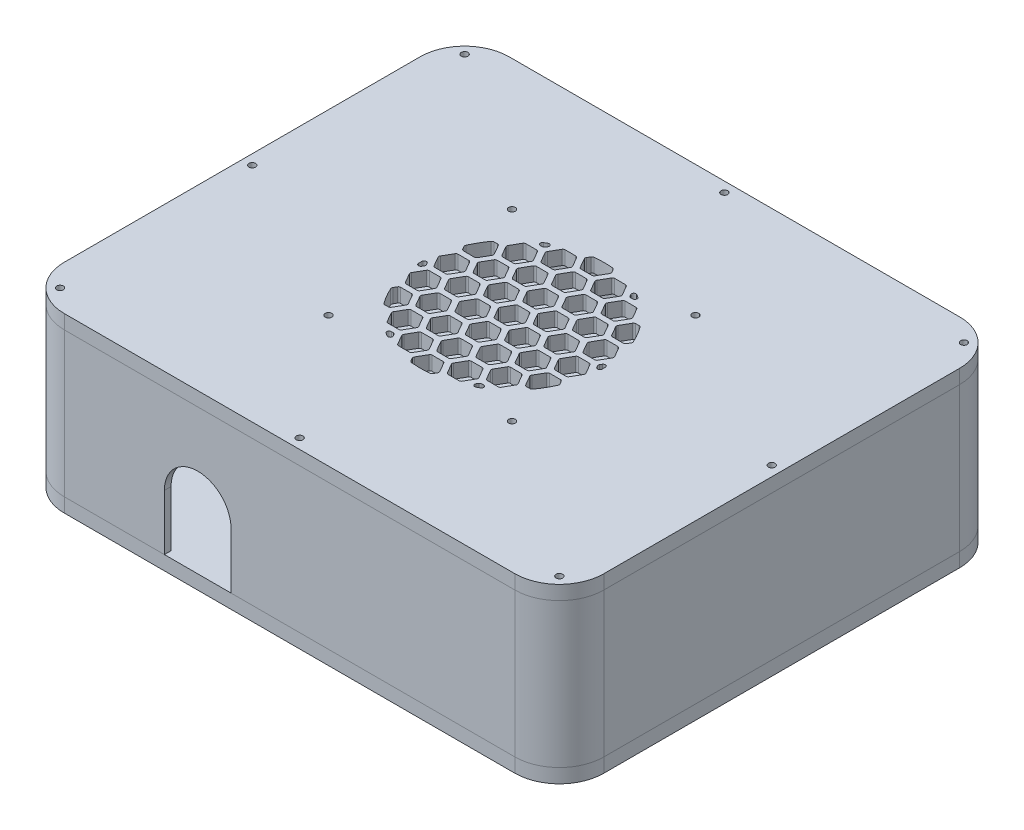
SolidWorks part; units mm, degrees
ref_plane "Front Plane" through (0, 0, 0) normal (0, 0, 1) x (1, 0, 0)
ref_plane "Top Plane" through (0, 0, 0) normal (0, 1, 0) x (1, 0, 0)
ref_plane "Right Plane" through (0, 0, 0) normal (1, 0, 0) x (0, 0, -1)
sketch "Sketch1" plane through (0, 0, 0) normal (0, 1, 0) x (1, 0, 0)
  line L0 (0, 100) -> (242.6, 100) construction
  line L1 (0, 0) -> (242.6, 0)
  line L2 (0, 0) -> (0, 200)
  line L3 (0, 200) -> (242.6, 200)
  line L4 (242.6, 0) -> (242.6, 200)
  line L6 (89, 170) -> (165.6, 170) construction
  line L7 (89, 170) -> (89, 15) construction
  line L8 (89, 15) -> (165.6, 15) construction
  line L9 (165.6, 170) -> (165.6, 15) construction
  line L10 (15, 106) -> (84, 106) construction
  line L11 (15, 106) -> (15, 15) construction
  line L12 (15, 15) -> (84, 15) construction
  line L13 (84, 106) -> (84, 15) construction
  line L14 (170.6, 184.9915) -> (230.6, 184.9915) construction
  line L15 (170.6, 184.9915) -> (170.6, 72.9915) construction
  line L16 (170.6, 72.9915) -> (230.6, 72.9915) construction
  line L17 (230.6, 184.9915) -> (230.6, 72.9915) construction
  line L22 (15, 170) -> (84, 170) construction
  line L23 (15, 170) -> (15, 121) construction
  line L24 (15, 121) -> (84, 121) construction
  line L25 (84, 170) -> (84, 121) construction
  dimension "D1" = 76.6
  dimension "D2" = 155
  dimension "D3" = 69
  dimension "D4" = 91
  dimension "D5" = 60
  dimension "D6" = 112
  dimension "D7" = 15
  dimension "D8" = 5
  dimension "D9" = 5
  dimension "D10" = 12
  dimension "D11" = 30
  dimension "D12" = 15
  dimension "D13" = 15
extrude "Boss-Extrude1" add sketch "Sketch1" along normal blind 6.35
fillet "Fillet1" radius 20 4 edges at (0, 3.175, -200) (242.6, 3.175, -200) (242.6, 3.175, 0) (0, 3.175, 0)
sketch "Sketch2" plane through (0, 6.35, 0) normal (0, 1, 0) x (1, 0, 0)
  line L0 (89, 170) -> (165.6, 170) construction
  line L1 (92.6, 160) -> (162, 160) construction
  line L2 (92.6, 160) -> (92.6, 18) construction
  line L3 (92.6, 18) -> (162, 18) construction
  line L4 (162, 160) -> (162, 18) construction
  line L5 (170.6, 184.9915) -> (230.6, 184.9915) construction
  line L6 (175.6, 150) -> (225.6, 150) construction
  line L7 (175.6, 150) -> (175.6, 125) construction
  line L8 (175.6, 125) -> (225.6, 125) construction
  line L9 (225.6, 150) -> (225.6, 125) construction
  line L10 (0, 200) -> (242.6, 200) construction
  line L11 (15, 170) -> (15, 121) construction
  line L12 (80.996, 125.18) -> (18.004, 125.18) construction
  line L13 (80.996, 125.18) -> (80.996, 165.82) construction
  line L14 (80.996, 165.82) -> (18.004, 165.82) construction
  line L15 (18.004, 125.18) -> (18.004, 165.82) construction
  line L16 (80.996, 125.18) -> (18.004, 165.82) construction
  line L17 (80.996, 165.82) -> (18.004, 125.18) construction
  line L18 (15, 170) -> (84, 170) construction
  line L19 (89, 15) -> (165.6, 15) construction
  circle A0 centre (92.6, 160) radius 1.5
  circle A1 centre (92.6, 18) radius 1.5
  circle A2 centre (162, 18) radius 1.5
  circle A3 centre (162, 160) radius 1.5
  circle A4 centre (175.6, 150) radius 1.5
  circle A5 centre (175.6, 125) radius 1.5
  circle A6 centre (225.6, 150) radius 1.5
  circle A7 centre (225.6, 125) radius 1.5
  circle A8 centre (18.004, 165.82) radius 1.5
  circle A9 centre (80.996, 165.82) radius 1.5
  circle A10 centre (80.996, 125.18) radius 1.5
  circle A11 centre (18.004, 125.18) radius 1.5
  point P6 (127.3, 160)
  point P7 (127.3, 170)
  point P20 (200.6, 150)
  point P23 (200.6, 184.9915)
  point P26 (49.5, 145.5)
  point P34 (15, 145.5)
  point P37 (49.5, 170)
  dimension "D6" = 3
  dimension "D1" = 69.4
  dimension "D2" = 142
  dimension "D3" = 3
  dimension "D4" = 50
  dimension "D5" = 25
  dimension "D7" = 50
  dimension "D8" = 62.992
  dimension "D9" = 40.64
extrude "Cut-Extrude1" cut sketch "Sketch2" against normal through all
sketch "Sketch3" plane through (0, 6.35, 0) normal (0, 1, 0) x (1, 0, 0)
  line L21 (20, 20) -> (9.0398, 9.0398) construction
  line L22 (0, 180) -> (0, 20) construction
  line L23 (6.565, 11.5147) -> (5.7618, 10.7116)
  line L24 (11.5147, 6.565) -> (10.7116, 5.7618)
  line L25 (0, 100) -> (242.6, 100) construction
  line L26 (121.3, 200) -> (121.3, 0) construction
  line L27 (231.0853, 6.565) -> (231.8884, 5.7618)
  line L28 (236.035, 11.5147) -> (236.8382, 10.7116)
  line L29 (236.035, 188.4853) -> (236.8382, 189.2884)
  line L30 (231.0853, 193.435) -> (231.8884, 194.2382)
  line L31 (11.5147, 193.435) -> (10.7116, 194.2382)
  line L32 (6.565, 188.4853) -> (5.7618, 189.2884)
  line L33 (242.6, 20) -> (242.6, 180) construction
  line L34 (20, 0) -> (222.6, 0) construction
  line L35 (222.6, 200) -> (20, 200) construction
  line L36 (20, 20) -> (20, 12.5101) construction
  line L37 (3, 180) -> (3, 20)
  line L38 (20, 3) -> (222.6, 3)
  line L39 (239.6, 20) -> (239.6, 180)
  line L40 (222.6, 197) -> (20, 197)
  line L41 (222.6, 200) -> (20, 200)
  line L42 (0, 180) -> (0, 20)
  line L43 (20, 0) -> (222.6, 0)
  line L44 (242.6, 20) -> (242.6, 180)
  line L45 (222.6, 200) -> (20, 200)
  line L46 (0, 180) -> (0, 20)
  line L47 (20, 0) -> (222.6, 0)
  line L48 (242.6, 20) -> (242.6, 180)
  line L49 (4.5, 103.5) -> (3, 103.5)
  line L50 (3, 103.5) -> (3, 96.5)
  line L51 (3, 96.5) -> (4.5, 96.5)
  line L52 (239.6, 103.5) -> (239.6, 96.5)
  line L53 (238.1, 103.5) -> (239.6, 103.5)
  line L54 (239.6, 96.5) -> (238.1, 96.5)
  line L55 (117.8, 195.5) -> (117.8, 197)
  line L56 (124.8, 195.5) -> (124.8, 197)
  line L57 (117.8, 197) -> (124.8, 197)
  line L58 (117.8, 4.5) -> (117.8, 3)
  line L59 (124.8, 4.5) -> (124.8, 3)
  line L60 (117.8, 3) -> (124.8, 3)
  arc A22 (10.7116, 194.2382) -> (5.7618, 189.2884) centre (20, 180) ccw
  arc A24 (5.7618, 10.7116) -> (10.7116, 5.7618) centre (20, 20) ccw
  arc A26 (231.8884, 5.7618) -> (236.8382, 10.7116) centre (222.6, 20) ccw
  arc A28 (236.8382, 189.2884) -> (231.8884, 194.2382) centre (222.6, 180) ccw
  arc A43 (11.5147, 6.565) -> (6.565, 11.5147) centre (9.0398, 9.0398) ccw
  circle A44 centre (9.0398, 9.0398) radius 1.5
  circle A45 centre (233.5602, 9.0398) radius 1.5
  arc A46 (231.0853, 6.565) -> (236.035, 11.5147) centre (233.5602, 9.0398) cw
  circle A47 centre (233.5602, 190.9602) radius 1.5
  arc A48 (231.0853, 193.435) -> (236.035, 188.4853) centre (233.5602, 190.9602) ccw
  circle A49 centre (9.0398, 190.9602) radius 1.5
  arc A50 (11.5147, 193.435) -> (6.565, 188.4853) centre (9.0398, 190.9602) cw
  arc A51 (222.6, 0) -> (242.6, 20) centre (222.6, 20) ccw construction
  arc A52 (0, 20) -> (20, 0) centre (20, 20) ccw construction
  arc A53 (242.6, 180) -> (222.6, 200) centre (222.6, 180) ccw construction
  arc A54 (20, 200) -> (0, 180) centre (20, 180) ccw construction
  arc A55 (3, 20) -> (20, 3) centre (20, 20) ccw
  arc A56 (222.6, 3) -> (239.6, 20) centre (222.6, 20) ccw
  arc A57 (239.6, 180) -> (222.6, 197) centre (222.6, 180) ccw
  arc A58 (20, 197) -> (3, 180) centre (20, 180) ccw
  arc A59 (20, 200) -> (0, 180) centre (20, 180) ccw
  arc A60 (0, 20) -> (20, 0) centre (20, 20) ccw
  arc A61 (222.6, 0) -> (242.6, 20) centre (222.6, 20) ccw
  arc A62 (242.6, 180) -> (222.6, 200) centre (222.6, 180) ccw
  arc A63 (20, 200) -> (0, 180) centre (20, 180) ccw
  arc A64 (0, 20) -> (20, 0) centre (20, 20) ccw
  arc A65 (222.6, 0) -> (242.6, 20) centre (222.6, 20) ccw
  arc A66 (242.6, 180) -> (222.6, 200) centre (222.6, 180) ccw
  arc A67 (4.5, 96.5) -> (4.5, 103.5) centre (4.5, 100) ccw
  circle A68 centre (4.5, 100) radius 1.5
  arc A69 (238.1, 96.5) -> (238.1, 103.5) centre (238.1, 100) cw
  circle A70 centre (238.1, 100) radius 1.5
  circle A71 centre (121.3, 195.5) radius 1.5
  arc A72 (117.8, 195.5) -> (124.8, 195.5) centre (121.3, 195.5) ccw
  circle A73 centre (121.3, 4.5) radius 1.5
  arc A74 (117.8, 4.5) -> (124.8, 4.5) centre (121.3, 4.5) cw
  line M50 (222.6, 200) -> (20, 200)
  arc M51 (20, 200) -> (0, 180) centre (20, 180) ccw
  line M52 (0, 180) -> (0, 20)
  arc M53 (0, 20) -> (20, 0) centre (20, 20) ccw
  line M54 (20, 0) -> (222.6, 0)
  arc M55 (222.6, 0) -> (242.6, 20) centre (222.6, 20) ccw
  line M56 (242.6, 20) -> (242.6, 180)
  arc M57 (242.6, 180) -> (222.6, 200) centre (222.6, 180) ccw
  dimension "D3" = 0
  dimension "D4" = 7
  dimension "D5" = 3
  dimension "D1" = 3
  dimension "D7" = 3
  dimension "D6" = 3
  dimension "D2" = 45
extrude "Boss-Extrude2" add sketch "Sketch3" along normal blind 65 separate body contours M57 M50 M51 M52 M53 M54 M55 M56 | A50 L31 A22 A49 L32 | L37 A68 L50 L51 A67 L49 | A24 A44 L24 A43 L23 | A46 L27 A26 A45 L28 | A74 L58 L38 A73 L60 L59 | L39 A70 L52 L53 A69 L54 | L30 A48 L29 A28 A47 | L55 A72 L56 L40 A71 L57 region at (11.4469, 6.35, -11.4469) region at (3.086, 6.35, -98.25) region at (117.886, 6.35, -3.75) region at (6.8741, 6.35, -190.6517) region at (231.5546, 6.35, -6.2312) region at (119.55, 6.35, -196.914) region at (238.85, 6.35, -96.586) region at (233.2517, 6.35, -193.1259) region at (236.5198, 6.35, -193.9198)
fillet "Fillet5" radius 2 16 edges at (10.7116, 38.85, -194.2382) (5.7618, 38.85, -189.2884) (3, 38.85, -103.5) (3, 38.85, -96.5) (5.7618, 38.85, -10.7116) (10.7116, 38.85, -5.7618) (117.8, 38.85, -3) (124.8, 38.85, -3) (231.8884, 38.85, -5.7618) (236.8382, 38.85, -10.7116) (239.6, 38.85, -96.5) (239.6, 38.85, -103.5) (231.8884, 38.85, -194.2382) (124.8, 38.85, -197) (117.8, 38.85, -197) (236.8382, 38.85, -189.2884)
sketch "Sketch4" plane through (0, 71.35, 0) normal (0, 1, 0) x (1, 0, 0)
  line L4 (0, 180) -> (0, 20)
  line L5 (222.6, 200) -> (20, 200)
  line L6 (242.6, 20) -> (242.6, 180)
  line L7 (20, 0) -> (222.6, 0)
  line L8 (0, 180) -> (0, 20)
  line L9 (222.6, 200) -> (20, 200)
  line L10 (242.6, 20) -> (242.6, 180)
  line L11 (20, 0) -> (222.6, 0)
  arc A4 (20, 200) -> (0, 180) centre (20, 180) ccw
  arc A5 (242.6, 180) -> (222.6, 200) centre (222.6, 180) ccw
  arc A6 (222.6, 0) -> (242.6, 20) centre (222.6, 20) ccw
  arc A7 (0, 20) -> (20, 0) centre (20, 20) ccw
  arc A8 (20, 200) -> (0, 180) centre (20, 180) ccw
  arc A9 (242.6, 180) -> (222.6, 200) centre (222.6, 180) ccw
  arc A10 (222.6, 0) -> (242.6, 20) centre (222.6, 20) ccw
  arc A11 (0, 20) -> (20, 0) centre (20, 20) ccw
  dimension "D1" = 0
extrude "Boss-Extrude4" add sketch "Sketch4" along normal blind 6.35 separate body
sketch "Sketch5" plane through (0, 77.7, 0) normal (0, 1, 0) x (1, 0, 0)
  line L1 (80.05, 141.25) -> (162.55, 141.25) construction
  line L2 (80.05, 141.25) -> (80.05, 58.75) construction
  line L3 (80.05, 58.75) -> (162.55, 58.75) construction
  line L4 (162.55, 141.25) -> (162.55, 58.75) construction
  line L5 (80.05, 141.25) -> (162.55, 58.75) construction
  line L6 (80.05, 58.75) -> (162.55, 141.25) construction
  line L8 (222.6, 200) -> (20, 200) construction
  line L9 (0, 180) -> (0, 20) construction
  circle A0 centre (80.05, 141.25) radius 1.5
  circle A1 centre (80.05, 58.75) radius 1.5
  circle A2 centre (162.55, 58.75) radius 1.5
  circle A3 centre (162.55, 141.25) radius 1.5
  point P0 (121.3, 100)
  point P11 (121.3, 200)
  point P12 (0, 100)
  dimension "D2" = 3
  dimension "D1" = 82.5
extrude "Cut-Extrude2" cut sketch "Sketch5" against normal through all
sketch "Sketch6" plane through (0, 77.7, 0) normal (0, 1, 0) x (1, 0, 0)
  circle A20 centre (121.3, 4.5) radius 1.5 construction
  circle A21 centre (233.5602, 9.0398) radius 1.5 construction
  circle A22 centre (238.1, 100) radius 1.5 construction
  circle A23 centre (233.5602, 190.9602) radius 1.5 construction
  circle A24 centre (121.3, 195.5) radius 1.5 construction
  circle A25 centre (9.0398, 190.9602) radius 1.5 construction
  circle A26 centre (4.5, 100) radius 1.5 construction
  circle A27 centre (9.0398, 9.0398) radius 1.5 construction
  circle A28 centre (121.3, 4.5) radius 1.5
  circle A29 centre (233.5602, 9.0398) radius 1.5
  circle A30 centre (238.1, 100) radius 1.5
  circle A31 centre (233.5602, 190.9602) radius 1.5
  circle A32 centre (121.3, 195.5) radius 1.5
  circle A33 centre (9.0398, 190.9602) radius 1.5
  circle A34 centre (4.5, 100) radius 1.5
  circle A35 centre (9.0398, 9.0398) radius 1.5
extrude "Cut-Extrude3" cut sketch "Sketch6" against normal through all
sketch "Sketch7" plane through (0, 77.7, 0) normal (0, 1, 0) x (1, 0, 0)
  line L0 (80.05, 141.25) -> (162.55, 141.25) construction
  line L1 (80.05, 141.25) -> (80.05, 58.75) construction
  line L2 (80.05, 58.75) -> (162.55, 58.75) construction
  line L3 (162.55, 141.25) -> (162.55, 58.75) construction
  line L4 (80.05, 141.25) -> (162.55, 141.25) construction
  line L5 (80.05, 141.25) -> (80.05, 58.75) construction
  line L6 (80.05, 58.75) -> (162.55, 58.75) construction
  line L7 (162.55, 141.25) -> (162.55, 58.75) construction
  line L8 (157.7952, 124.5346) -> (151.7952, 124.5346)
  line L9 (124.3, 105.1962) -> (118.3, 105.1962)
  line L10 (118.3, 105.1962) -> (115.3, 100)
  line L11 (115.3, 100) -> (118.3, 94.8038)
  line L12 (118.3, 94.8038) -> (124.3, 94.8038)
  line L13 (124.3, 94.8038) -> (127.3, 100)
  line L14 (127.3, 100) -> (124.3, 105.1962)
  line L15 (138.4651, 106.4462) -> (135.4651, 111.6423)
  line L16 (135.4651, 111.6423) -> (129.4651, 111.6423)
  line L17 (129.4651, 111.6423) -> (126.4651, 106.4462)
  line L18 (126.4651, 106.4462) -> (129.4651, 101.25)
  line L19 (129.4651, 101.25) -> (135.4651, 101.25)
  line L20 (135.4651, 101.25) -> (138.4651, 106.4462)
  line L21 (127.3, 112.8923) -> (124.3, 118.0885)
  line L22 (124.3, 118.0885) -> (118.3, 118.0885)
  line L23 (118.3, 118.0885) -> (115.3, 112.8923)
  line L24 (115.3, 112.8923) -> (118.3, 107.6962)
  line L25 (118.3, 107.6962) -> (124.3, 107.6962)
  line L26 (124.3, 107.6962) -> (127.3, 112.8923)
  line L27 (135.4651, 124.5346) -> (129.4651, 124.5346)
  line L28 (129.4651, 124.5346) -> (126.4651, 119.3385)
  line L29 (126.4651, 119.3385) -> (129.4651, 114.1423)
  line L30 (129.4651, 114.1423) -> (135.4651, 114.1423)
  line L31 (135.4651, 114.1423) -> (138.4651, 119.3385)
  line L32 (138.4651, 119.3385) -> (135.4651, 124.5346)
  line L33 (151.7952, 124.5346) -> (148.7952, 119.3385)
  line L34 (148.7952, 119.3385) -> (151.7952, 114.1423)
  line L35 (151.7952, 114.1423) -> (157.7952, 114.1423)
  line L36 (157.7952, 114.1423) -> (160.7952, 119.3385)
  line L37 (160.7952, 119.3385) -> (157.7952, 124.5346)
  line L38 (149.6301, 112.8923) -> (146.6301, 118.0885)
  line L39 (146.6301, 118.0885) -> (140.6301, 118.0885)
  line L40 (140.6301, 118.0885) -> (137.6301, 112.8923)
  line L41 (137.6301, 112.8923) -> (140.6301, 107.6962)
  line L42 (140.6301, 107.6962) -> (146.6301, 107.6962)
  line L43 (146.6301, 107.6962) -> (149.6301, 112.8923)
  line L44 (146.6301, 105.1962) -> (140.6301, 105.1962)
  line L45 (140.6301, 105.1962) -> (137.6301, 100)
  line L46 (137.6301, 100) -> (140.6301, 94.8038)
  line L47 (140.6301, 94.8038) -> (146.6301, 94.8038)
  line L48 (146.6301, 94.8038) -> (149.6301, 100)
  line L49 (149.6301, 100) -> (146.6301, 105.1962)
  line L50 (160.7952, 106.4462) -> (157.7952, 111.6423)
  line L51 (157.7952, 111.6423) -> (151.7952, 111.6423)
  line L52 (151.7952, 111.6423) -> (148.7952, 106.4462)
  line L53 (148.7952, 106.4462) -> (151.7952, 101.25)
  line L54 (151.7952, 101.25) -> (157.7952, 101.25)
  line L55 (157.7952, 101.25) -> (160.7952, 106.4462)
  line L56 (180.1253, 124.5346) -> (174.1253, 124.5346)
  line L57 (174.1253, 124.5346) -> (171.1253, 119.3385)
  line L58 (171.1253, 119.3385) -> (174.1253, 114.1423)
  line L59 (174.1253, 114.1423) -> (180.1253, 114.1423)
  line L60 (180.1253, 114.1423) -> (183.1253, 119.3385)
  line L61 (183.1253, 119.3385) -> (180.1253, 124.5346)
  line L62 (171.9603, 112.8923) -> (168.9603, 118.0885)
  line L63 (168.9603, 118.0885) -> (162.9603, 118.0885)
  line L64 (162.9603, 118.0885) -> (159.9603, 112.8923)
  line L65 (159.9603, 112.8923) -> (162.9603, 107.6962)
  line L66 (162.9603, 107.6962) -> (168.9603, 107.6962)
  line L67 (168.9603, 107.6962) -> (171.9603, 112.8923)
  line L68 (168.9603, 105.1962) -> (162.9603, 105.1962)
  line L69 (162.9603, 105.1962) -> (159.9603, 100)
  line L70 (159.9603, 100) -> (162.9603, 94.8038)
  line L71 (162.9603, 94.8038) -> (168.9603, 94.8038)
  line L72 (168.9603, 94.8038) -> (171.9603, 100)
  line L73 (171.9603, 100) -> (168.9603, 105.1962)
  line L74 (183.1253, 106.4462) -> (180.1253, 111.6423)
  line L75 (180.1253, 111.6423) -> (174.1253, 111.6423)
  line L76 (174.1253, 111.6423) -> (171.1253, 106.4462)
  line L77 (171.1253, 106.4462) -> (174.1253, 101.25)
  line L78 (174.1253, 101.25) -> (180.1253, 101.25)
  line L79 (180.1253, 101.25) -> (183.1253, 106.4462)
  line L80 (157.7952, 150.3192) -> (151.7952, 150.3192)
  line L81 (151.7952, 150.3192) -> (148.7952, 145.1231)
  line L82 (148.7952, 145.1231) -> (151.7952, 139.9269)
  line L83 (151.7952, 139.9269) -> (157.7952, 139.9269)
  line L84 (157.7952, 139.9269) -> (160.7952, 145.1231)
  line L85 (160.7952, 145.1231) -> (157.7952, 150.3192)
  line L86 (149.6301, 138.6769) -> (146.6301, 143.8731)
  line L87 (146.6301, 143.8731) -> (140.6301, 143.8731)
  line L88 (140.6301, 143.8731) -> (137.6301, 138.6769)
  line L89 (137.6301, 138.6769) -> (140.6301, 133.4808)
  line L90 (140.6301, 133.4808) -> (146.6301, 133.4808)
  line L91 (146.6301, 133.4808) -> (149.6301, 138.6769)
  line L92 (146.6301, 130.9808) -> (140.6301, 130.9808)
  line L93 (140.6301, 130.9808) -> (137.6301, 125.7846)
  line L94 (137.6301, 125.7846) -> (140.6301, 120.5885)
  line L95 (140.6301, 120.5885) -> (146.6301, 120.5885)
  line L96 (146.6301, 120.5885) -> (149.6301, 125.7846)
  line L97 (149.6301, 125.7846) -> (146.6301, 130.9808)
  line L98 (160.7952, 132.2308) -> (157.7952, 137.4269)
  line L99 (157.7952, 137.4269) -> (151.7952, 137.4269)
  line L100 (151.7952, 137.4269) -> (148.7952, 132.2308)
  line L101 (148.7952, 132.2308) -> (151.7952, 127.0346)
  line L102 (151.7952, 127.0346) -> (157.7952, 127.0346)
  line L103 (157.7952, 127.0346) -> (160.7952, 132.2308)
  line L104 (180.1253, 150.3192) -> (174.1253, 150.3192)
  line L105 (174.1253, 150.3192) -> (171.1253, 145.1231)
  line L106 (171.1253, 145.1231) -> (174.1253, 139.9269)
  line L107 (174.1253, 139.9269) -> (180.1253, 139.9269)
  line L108 (180.1253, 139.9269) -> (183.1253, 145.1231)
  line L109 (183.1253, 145.1231) -> (180.1253, 150.3192)
  line L110 (171.9603, 138.6769) -> (168.9603, 143.8731)
  line L111 (168.9603, 143.8731) -> (162.9603, 143.8731)
  line L112 (162.9603, 143.8731) -> (159.9603, 138.6769)
  line L113 (159.9603, 138.6769) -> (162.9603, 133.4808)
  line L114 (162.9603, 133.4808) -> (168.9603, 133.4808)
  line L115 (168.9603, 133.4808) -> (171.9603, 138.6769)
  line L116 (168.9603, 130.9808) -> (162.9603, 130.9808)
  line L117 (162.9603, 130.9808) -> (159.9603, 125.7846)
  line L118 (159.9603, 125.7846) -> (162.9603, 120.5885)
  line L119 (162.9603, 120.5885) -> (168.9603, 120.5885)
  line L120 (168.9603, 120.5885) -> (171.9603, 125.7846)
  line L121 (171.9603, 125.7846) -> (168.9603, 130.9808)
  line L122 (183.1253, 132.2308) -> (180.1253, 137.4269)
  line L123 (180.1253, 137.4269) -> (174.1253, 137.4269)
  line L124 (174.1253, 137.4269) -> (171.1253, 132.2308)
  line L125 (171.1253, 132.2308) -> (174.1253, 127.0346)
  line L126 (174.1253, 127.0346) -> (180.1253, 127.0346)
  line L127 (180.1253, 127.0346) -> (183.1253, 132.2308)
  line L128 (135.4651, 150.3192) -> (129.4651, 150.3192)
  line L129 (129.4651, 150.3192) -> (126.4651, 145.1231)
  line L130 (126.4651, 145.1231) -> (129.4651, 139.9269)
  line L131 (129.4651, 139.9269) -> (135.4651, 139.9269)
  line L132 (135.4651, 139.9269) -> (138.4651, 145.1231)
  line L133 (138.4651, 145.1231) -> (135.4651, 150.3192)
  line L134 (127.3, 138.6769) -> (124.3, 143.8731)
  line L135 (124.3, 143.8731) -> (118.3, 143.8731)
  line L136 (118.3, 143.8731) -> (115.3, 138.6769)
  line L137 (115.3, 138.6769) -> (118.3, 133.4808)
  line L138 (118.3, 133.4808) -> (124.3, 133.4808)
  line L139 (124.3, 133.4808) -> (127.3, 138.6769)
  line L140 (124.3, 130.9808) -> (118.3, 130.9808)
  line L141 (118.3, 130.9808) -> (115.3, 125.7846)
  line L142 (115.3, 125.7846) -> (118.3, 120.5885)
  line L143 (118.3, 120.5885) -> (124.3, 120.5885)
  line L144 (124.3, 120.5885) -> (127.3, 125.7846)
  line L145 (127.3, 125.7846) -> (124.3, 130.9808)
  line L146 (138.4651, 132.2308) -> (135.4651, 137.4269)
  line L147 (135.4651, 137.4269) -> (129.4651, 137.4269)
  line L148 (129.4651, 137.4269) -> (126.4651, 132.2308)
  line L149 (126.4651, 132.2308) -> (129.4651, 127.0346)
  line L150 (129.4651, 127.0346) -> (135.4651, 127.0346)
  line L151 (135.4651, 127.0346) -> (138.4651, 132.2308)
  line L152 (124.3, 92.3038) -> (118.3, 92.3038)
  line L153 (118.3, 92.3038) -> (115.3, 87.1077)
  line L154 (115.3, 87.1077) -> (118.3, 81.9115)
  line L155 (118.3, 81.9115) -> (124.3, 81.9115)
  line L156 (124.3, 81.9115) -> (127.3, 87.1077)
  line L157 (127.3, 87.1077) -> (124.3, 92.3038)
  line L158 (138.4651, 93.5538) -> (135.4651, 98.75)
  line L159 (135.4651, 98.75) -> (129.4651, 98.75)
  line L160 (129.4651, 98.75) -> (126.4651, 93.5538)
  line L161 (126.4651, 93.5538) -> (129.4651, 88.3577)
  line L162 (129.4651, 88.3577) -> (135.4651, 88.3577)
  line L163 (135.4651, 88.3577) -> (138.4651, 93.5538)
  line L164 (160.7952, 93.5538) -> (157.7952, 98.75)
  line L165 (157.7952, 98.75) -> (151.7952, 98.75)
  line L166 (151.7952, 98.75) -> (148.7952, 93.5538)
  line L167 (148.7952, 93.5538) -> (151.7952, 88.3577)
  line L168 (151.7952, 88.3577) -> (157.7952, 88.3577)
  line L169 (157.7952, 88.3577) -> (160.7952, 93.5538)
  line L170 (168.9603, 92.3038) -> (162.9603, 92.3038)
  line L171 (162.9603, 92.3038) -> (159.9603, 87.1077)
  line L172 (159.9603, 87.1077) -> (162.9603, 81.9115)
  line L173 (162.9603, 81.9115) -> (168.9603, 81.9115)
  line L174 (168.9603, 81.9115) -> (171.9603, 87.1077)
  line L175 (171.9603, 87.1077) -> (168.9603, 92.3038)
  line L176 (146.6301, 92.3038) -> (140.6301, 92.3038)
  line L177 (140.6301, 92.3038) -> (137.6301, 87.1077)
  line L178 (137.6301, 87.1077) -> (140.6301, 81.9115)
  line L179 (140.6301, 81.9115) -> (146.6301, 81.9115)
  line L180 (146.6301, 81.9115) -> (149.6301, 87.1077)
  line L181 (149.6301, 87.1077) -> (146.6301, 92.3038)
  line L182 (124.3, 79.4115) -> (118.3, 79.4115)
  line L183 (118.3, 79.4115) -> (115.3, 74.2154)
  line L184 (115.3, 74.2154) -> (118.3, 69.0192)
  line L185 (118.3, 69.0192) -> (124.3, 69.0192)
  line L186 (124.3, 69.0192) -> (127.3, 74.2154)
  line L187 (127.3, 74.2154) -> (124.3, 79.4115)
  line L188 (138.4651, 80.6615) -> (135.4651, 85.8577)
  line L189 (135.4651, 85.8577) -> (129.4651, 85.8577)
  line L190 (129.4651, 85.8577) -> (126.4651, 80.6615)
  line L191 (126.4651, 80.6615) -> (129.4651, 75.4654)
  line L192 (129.4651, 75.4654) -> (135.4651, 75.4654)
  line L193 (135.4651, 75.4654) -> (138.4651, 80.6615)
  line L194 (160.7952, 80.6615) -> (157.7952, 85.8577)
  line L195 (157.7952, 85.8577) -> (151.7952, 85.8577)
  line L196 (151.7952, 85.8577) -> (148.7952, 80.6615)
  line L197 (148.7952, 80.6615) -> (151.7952, 75.4654)
  line L198 (151.7952, 75.4654) -> (157.7952, 75.4654)
  line L199 (157.7952, 75.4654) -> (160.7952, 80.6615)
  line L200 (168.9603, 79.4115) -> (162.9603, 79.4115)
  line L201 (162.9603, 79.4115) -> (159.9603, 74.2154)
  line L202 (159.9603, 74.2154) -> (162.9603, 69.0192)
  line L203 (162.9603, 69.0192) -> (168.9603, 69.0192)
  line L204 (168.9603, 69.0192) -> (171.9603, 74.2154)
  line L205 (171.9603, 74.2154) -> (168.9603, 79.4115)
  line L206 (146.6301, 79.4115) -> (140.6301, 79.4115)
  line L207 (140.6301, 79.4115) -> (137.6301, 74.2154)
  line L208 (137.6301, 74.2154) -> (140.6301, 69.0192)
  line L209 (140.6301, 69.0192) -> (146.6301, 69.0192)
  line L210 (146.6301, 69.0192) -> (149.6301, 74.2154)
  line L211 (149.6301, 74.2154) -> (146.6301, 79.4115)
  line L212 (124.3, 66.5192) -> (118.3, 66.5192)
  line L213 (118.3, 66.5192) -> (115.3, 61.3231)
  line L214 (115.3, 61.3231) -> (118.3, 56.1269)
  line L215 (118.3, 56.1269) -> (124.3, 56.1269)
  line L216 (124.3, 56.1269) -> (127.3, 61.3231)
  line L217 (127.3, 61.3231) -> (124.3, 66.5192)
  line L218 (138.4651, 67.7692) -> (135.4651, 72.9654)
  line L219 (135.4651, 72.9654) -> (129.4651, 72.9654)
  line L220 (129.4651, 72.9654) -> (126.4651, 67.7692)
  line L221 (126.4651, 67.7692) -> (129.4651, 62.5731)
  line L222 (129.4651, 62.5731) -> (135.4651, 62.5731)
  line L223 (135.4651, 62.5731) -> (138.4651, 67.7692)
  line L224 (160.7952, 67.7692) -> (157.7952, 72.9654)
  line L225 (157.7952, 72.9654) -> (151.7952, 72.9654)
  line L226 (151.7952, 72.9654) -> (148.7952, 67.7692)
  line L227 (148.7952, 67.7692) -> (151.7952, 62.5731)
  line L228 (151.7952, 62.5731) -> (157.7952, 62.5731)
  line L229 (157.7952, 62.5731) -> (160.7952, 67.7692)
  line L230 (168.9603, 66.5192) -> (162.9603, 66.5192)
  line L231 (162.9603, 66.5192) -> (159.9603, 61.3231)
  line L232 (159.9603, 61.3231) -> (162.9603, 56.1269)
  line L233 (162.9603, 56.1269) -> (168.9603, 56.1269)
  line L234 (168.9603, 56.1269) -> (171.9603, 61.3231)
  line L235 (171.9603, 61.3231) -> (168.9603, 66.5192)
  line L236 (146.6301, 66.5192) -> (140.6301, 66.5192)
  line L237 (140.6301, 66.5192) -> (137.6301, 61.3231)
  line L238 (137.6301, 61.3231) -> (140.6301, 56.1269)
  line L239 (140.6301, 56.1269) -> (146.6301, 56.1269)
  line L240 (146.6301, 56.1269) -> (149.6301, 61.3231)
  line L241 (149.6301, 61.3231) -> (146.6301, 66.5192)
  line L242 (124.3, 53.6269) -> (118.3, 53.6269)
  line L243 (118.3, 53.6269) -> (115.3, 48.4308)
  line L244 (115.3, 48.4308) -> (118.3, 43.2346)
  line L245 (118.3, 43.2346) -> (124.3, 43.2346)
  line L246 (124.3, 43.2346) -> (127.3, 48.4308)
  line L247 (127.3, 48.4308) -> (124.3, 53.6269)
  line L248 (138.4651, 54.8769) -> (135.4651, 60.0731)
  line L249 (135.4651, 60.0731) -> (129.4651, 60.0731)
  line L250 (129.4651, 60.0731) -> (126.4651, 54.8769)
  line L251 (126.4651, 54.8769) -> (129.4651, 49.6808)
  line L252 (129.4651, 49.6808) -> (135.4651, 49.6808)
  line L253 (135.4651, 49.6808) -> (138.4651, 54.8769)
  line L254 (160.7952, 54.8769) -> (157.7952, 60.0731)
  line L255 (157.7952, 60.0731) -> (151.7952, 60.0731)
  line L256 (151.7952, 60.0731) -> (148.7952, 54.8769)
  line L257 (148.7952, 54.8769) -> (151.7952, 49.6808)
  line L258 (151.7952, 49.6808) -> (157.7952, 49.6808)
  line L259 (157.7952, 49.6808) -> (160.7952, 54.8769)
  line L260 (168.9603, 53.6269) -> (162.9603, 53.6269)
  line L261 (162.9603, 53.6269) -> (159.9603, 48.4308)
  line L262 (159.9603, 48.4308) -> (162.9603, 43.2346)
  line L263 (162.9603, 43.2346) -> (168.9603, 43.2346)
  line L264 (168.9603, 43.2346) -> (171.9603, 48.4308)
  line L265 (171.9603, 48.4308) -> (168.9603, 53.6269)
  line L266 (146.6301, 53.6269) -> (140.6301, 53.6269)
  line L267 (140.6301, 53.6269) -> (137.6301, 48.4308)
  line L268 (137.6301, 48.4308) -> (140.6301, 43.2346)
  line L269 (140.6301, 43.2346) -> (146.6301, 43.2346)
  line L270 (146.6301, 43.2346) -> (149.6301, 48.4308)
  line L271 (149.6301, 48.4308) -> (146.6301, 53.6269)
  line L272 (104.9699, 138.6769) -> (101.9699, 143.8731)
  line L273 (101.9699, 143.8731) -> (95.9699, 143.8731)
  line L274 (95.9699, 143.8731) -> (92.9699, 138.6769)
  line L275 (92.9699, 138.6769) -> (95.9699, 133.4808)
  line L276 (95.9699, 133.4808) -> (101.9699, 133.4808)
  line L277 (101.9699, 133.4808) -> (104.9699, 138.6769)
  line L278 (101.9699, 130.9808) -> (95.9699, 130.9808)
  line L279 (95.9699, 130.9808) -> (92.9699, 125.7846)
  line L280 (92.9699, 125.7846) -> (95.9699, 120.5885)
  line L281 (95.9699, 120.5885) -> (101.9699, 120.5885)
  line L282 (101.9699, 120.5885) -> (104.9699, 125.7846)
  line L283 (104.9699, 125.7846) -> (101.9699, 130.9808)
  line L284 (101.9699, 92.3038) -> (95.9699, 92.3038)
  line L285 (95.9699, 92.3038) -> (92.9699, 87.1077)
  line L286 (92.9699, 87.1077) -> (95.9699, 81.9115)
  line L287 (95.9699, 81.9115) -> (101.9699, 81.9115)
  line L288 (101.9699, 81.9115) -> (104.9699, 87.1077)
  line L289 (104.9699, 87.1077) -> (101.9699, 92.3038)
  line L290 (101.9699, 79.4115) -> (95.9699, 79.4115)
  line L291 (95.9699, 79.4115) -> (92.9699, 74.2154)
  line L292 (92.9699, 74.2154) -> (95.9699, 69.0192)
  line L293 (95.9699, 69.0192) -> (101.9699, 69.0192)
  line L294 (101.9699, 69.0192) -> (104.9699, 74.2154)
  line L295 (104.9699, 74.2154) -> (101.9699, 79.4115)
  line L296 (101.9699, 66.5192) -> (95.9699, 66.5192)
  line L297 (95.9699, 66.5192) -> (92.9699, 61.3231)
  line L298 (92.9699, 61.3231) -> (95.9699, 56.1269)
  line L299 (95.9699, 56.1269) -> (101.9699, 56.1269)
  line L300 (101.9699, 56.1269) -> (104.9699, 61.3231)
  line L301 (104.9699, 61.3231) -> (101.9699, 66.5192)
  line L302 (116.1349, 67.7692) -> (113.1349, 72.9654)
  line L303 (113.1349, 72.9654) -> (107.1349, 72.9654)
  line L304 (107.1349, 72.9654) -> (104.1349, 67.7692)
  line L305 (104.1349, 67.7692) -> (107.1349, 62.5731)
  line L306 (107.1349, 62.5731) -> (113.1349, 62.5731)
  line L307 (113.1349, 62.5731) -> (116.1349, 67.7692)
  line L308 (116.1349, 80.6615) -> (113.1349, 85.8577)
  line L309 (113.1349, 85.8577) -> (107.1349, 85.8577)
  line L310 (107.1349, 85.8577) -> (104.1349, 80.6615)
  line L311 (104.1349, 80.6615) -> (107.1349, 75.4654)
  line L312 (107.1349, 75.4654) -> (113.1349, 75.4654)
  line L313 (113.1349, 75.4654) -> (116.1349, 80.6615)
  line L314 (101.9699, 105.1962) -> (95.9699, 105.1962)
  line L315 (95.9699, 105.1962) -> (92.9699, 100)
  line L316 (92.9699, 100) -> (95.9699, 94.8038)
  line L317 (95.9699, 94.8038) -> (101.9699, 94.8038)
  line L318 (101.9699, 94.8038) -> (104.9699, 100)
  line L319 (104.9699, 100) -> (101.9699, 105.1962)
  line L320 (116.1349, 93.5538) -> (113.1349, 98.75)
  line L321 (113.1349, 98.75) -> (107.1349, 98.75)
  line L322 (107.1349, 98.75) -> (104.1349, 93.5538)
  line L323 (104.1349, 93.5538) -> (107.1349, 88.3577)
  line L324 (107.1349, 88.3577) -> (113.1349, 88.3577)
  line L325 (113.1349, 88.3577) -> (116.1349, 93.5538)
  line L326 (116.1349, 106.4462) -> (113.1349, 111.6423)
  line L327 (113.1349, 111.6423) -> (107.1349, 111.6423)
  line L328 (107.1349, 111.6423) -> (104.1349, 106.4462)
  line L329 (104.1349, 106.4462) -> (107.1349, 101.25)
  line L330 (107.1349, 101.25) -> (113.1349, 101.25)
  line L331 (113.1349, 101.25) -> (116.1349, 106.4462)
  line L332 (104.9699, 112.8923) -> (101.9699, 118.0885)
  line L333 (101.9699, 118.0885) -> (95.9699, 118.0885)
  line L334 (95.9699, 118.0885) -> (92.9699, 112.8923)
  line L335 (92.9699, 112.8923) -> (95.9699, 107.6962)
  line L336 (95.9699, 107.6962) -> (101.9699, 107.6962)
  line L337 (101.9699, 107.6962) -> (104.9699, 112.8923)
  line L338 (113.1349, 124.5346) -> (107.1349, 124.5346)
  line L339 (107.1349, 124.5346) -> (104.1349, 119.3385)
  line L340 (104.1349, 119.3385) -> (107.1349, 114.1423)
  line L341 (107.1349, 114.1423) -> (113.1349, 114.1423)
  line L342 (113.1349, 114.1423) -> (116.1349, 119.3385)
  line L343 (116.1349, 119.3385) -> (113.1349, 124.5346)
  line L344 (116.1349, 132.2308) -> (113.1349, 137.4269)
  line L345 (113.1349, 137.4269) -> (107.1349, 137.4269)
  line L346 (107.1349, 137.4269) -> (104.1349, 132.2308)
  line L347 (104.1349, 132.2308) -> (107.1349, 127.0346)
  line L348 (107.1349, 127.0346) -> (113.1349, 127.0346)
  line L349 (113.1349, 127.0346) -> (116.1349, 132.2308)
  line L350 (116.1349, 54.8769) -> (113.1349, 60.0731)
  line L351 (113.1349, 60.0731) -> (107.1349, 60.0731)
  line L352 (107.1349, 60.0731) -> (104.1349, 54.8769)
  line L353 (104.1349, 54.8769) -> (107.1349, 49.6808)
  line L354 (107.1349, 49.6808) -> (113.1349, 49.6808)
  line L355 (113.1349, 49.6808) -> (116.1349, 54.8769)
  line L356 (82.6397, 138.6769) -> (79.6397, 143.8731)
  line L357 (79.6397, 143.8731) -> (73.6397, 143.8731)
  line L358 (73.6397, 143.8731) -> (70.6397, 138.6769)
  line L359 (70.6397, 138.6769) -> (73.6397, 133.4808)
  line L360 (73.6397, 133.4808) -> (79.6397, 133.4808)
  line L361 (79.6397, 133.4808) -> (82.6397, 138.6769)
  line L362 (79.6397, 130.9808) -> (73.6397, 130.9808)
  line L363 (73.6397, 130.9808) -> (70.6397, 125.7846)
  line L364 (70.6397, 125.7846) -> (73.6397, 120.5885)
  line L365 (73.6397, 120.5885) -> (79.6397, 120.5885)
  line L366 (79.6397, 120.5885) -> (82.6397, 125.7846)
  line L367 (82.6397, 125.7846) -> (79.6397, 130.9808)
  line L368 (79.6397, 92.3038) -> (73.6397, 92.3038)
  line L369 (73.6397, 92.3038) -> (70.6397, 87.1077)
  line L370 (70.6397, 87.1077) -> (73.6397, 81.9115)
  line L371 (73.6397, 81.9115) -> (79.6397, 81.9115)
  line L372 (79.6397, 81.9115) -> (82.6397, 87.1077)
  line L373 (82.6397, 87.1077) -> (79.6397, 92.3038)
  line L374 (79.6397, 79.4115) -> (73.6397, 79.4115)
  line L375 (73.6397, 79.4115) -> (70.6397, 74.2154)
  line L376 (70.6397, 74.2154) -> (73.6397, 69.0192)
  line L377 (73.6397, 69.0192) -> (79.6397, 69.0192)
  line L378 (79.6397, 69.0192) -> (82.6397, 74.2154)
  line L379 (82.6397, 74.2154) -> (79.6397, 79.4115)
  line L380 (79.6397, 66.5192) -> (73.6397, 66.5192)
  line L381 (73.6397, 66.5192) -> (70.6397, 61.3231)
  line L382 (70.6397, 61.3231) -> (73.6397, 56.1269)
  line L383 (73.6397, 56.1269) -> (79.6397, 56.1269)
  line L384 (79.6397, 56.1269) -> (82.6397, 61.3231)
  line L385 (82.6397, 61.3231) -> (79.6397, 66.5192)
  line L386 (93.8048, 67.7692) -> (90.8048, 72.9654)
  line L387 (90.8048, 72.9654) -> (84.8048, 72.9654)
  line L388 (84.8048, 72.9654) -> (81.8048, 67.7692)
  line L389 (81.8048, 67.7692) -> (84.8048, 62.5731)
  line L390 (84.8048, 62.5731) -> (90.8048, 62.5731)
  line L391 (90.8048, 62.5731) -> (93.8048, 67.7692)
  line L392 (93.8048, 80.6615) -> (90.8048, 85.8577)
  line L393 (90.8048, 85.8577) -> (84.8048, 85.8577)
  line L394 (84.8048, 85.8577) -> (81.8048, 80.6615)
  line L395 (81.8048, 80.6615) -> (84.8048, 75.4654)
  line L396 (84.8048, 75.4654) -> (90.8048, 75.4654)
  line L397 (90.8048, 75.4654) -> (93.8048, 80.6615)
  line L398 (79.6397, 105.1962) -> (73.6397, 105.1962)
  line L399 (73.6397, 105.1962) -> (70.6397, 100)
  line L400 (70.6397, 100) -> (73.6397, 94.8038)
  line L401 (73.6397, 94.8038) -> (79.6397, 94.8038)
  line L402 (79.6397, 94.8038) -> (82.6397, 100)
  line L403 (82.6397, 100) -> (79.6397, 105.1962)
  line L404 (93.8048, 93.5538) -> (90.8048, 98.75)
  line L405 (90.8048, 98.75) -> (84.8048, 98.75)
  line L406 (84.8048, 98.75) -> (81.8048, 93.5538)
  line L407 (81.8048, 93.5538) -> (84.8048, 88.3577)
  line L408 (84.8048, 88.3577) -> (90.8048, 88.3577)
  line L409 (90.8048, 88.3577) -> (93.8048, 93.5538)
  line L410 (93.8048, 106.4462) -> (90.8048, 111.6423)
  line L411 (90.8048, 111.6423) -> (84.8048, 111.6423)
  line L412 (84.8048, 111.6423) -> (81.8048, 106.4462)
  line L413 (81.8048, 106.4462) -> (84.8048, 101.25)
  line L414 (84.8048, 101.25) -> (90.8048, 101.25)
  line L415 (90.8048, 101.25) -> (93.8048, 106.4462)
  line L416 (82.6397, 112.8923) -> (79.6397, 118.0885)
  line L417 (79.6397, 118.0885) -> (73.6397, 118.0885)
  line L418 (73.6397, 118.0885) -> (70.6397, 112.8923)
  line L419 (70.6397, 112.8923) -> (73.6397, 107.6962)
  line L420 (73.6397, 107.6962) -> (79.6397, 107.6962)
  line L421 (79.6397, 107.6962) -> (82.6397, 112.8923)
  line L422 (90.8048, 124.5346) -> (84.8048, 124.5346)
  line L423 (84.8048, 124.5346) -> (81.8048, 119.3385)
  line L424 (81.8048, 119.3385) -> (84.8048, 114.1423)
  line L425 (84.8048, 114.1423) -> (90.8048, 114.1423)
  line L426 (90.8048, 114.1423) -> (93.8048, 119.3385)
  line L427 (93.8048, 119.3385) -> (90.8048, 124.5346)
  line L428 (93.8048, 132.2308) -> (90.8048, 137.4269)
  line L429 (90.8048, 137.4269) -> (84.8048, 137.4269)
  line L430 (84.8048, 137.4269) -> (81.8048, 132.2308)
  line L431 (81.8048, 132.2308) -> (84.8048, 127.0346)
  line L432 (84.8048, 127.0346) -> (90.8048, 127.0346)
  line L433 (90.8048, 127.0346) -> (93.8048, 132.2308)
  line L434 (93.8048, 54.8769) -> (90.8048, 60.0731)
  line L435 (90.8048, 60.0731) -> (84.8048, 60.0731)
  line L436 (84.8048, 60.0731) -> (81.8048, 54.8769)
  line L437 (81.8048, 54.8769) -> (84.8048, 49.6808)
  line L438 (84.8048, 49.6808) -> (90.8048, 49.6808)
  line L439 (90.8048, 49.6808) -> (93.8048, 54.8769)
  line L440 (116.1349, 145.1231) -> (113.1349, 150.3192)
  line L441 (113.1349, 150.3192) -> (107.1349, 150.3192)
  line L442 (107.1349, 150.3192) -> (104.1349, 145.1231)
  line L443 (104.1349, 145.1231) -> (107.1349, 139.9269)
  line L444 (107.1349, 139.9269) -> (113.1349, 139.9269)
  line L445 (113.1349, 139.9269) -> (116.1349, 145.1231)
  circle A0 centre (121.3, 100) radius 41.25
  circle A4 centre (121.3, 100) radius 5.1962 construction
  circle A5 centre (132.4651, 106.4462) radius 5.1962 construction
  circle A6 centre (121.3, 112.8923) radius 5.1962 construction
  circle A7 centre (132.4651, 119.3385) radius 5.1962 construction
  point P15 (125.8, 115.4904)
  dimension "D1" = 6
  dimension "D2" = 2.5
  dimension "D3" = 1.25
  dimension "D4" = 2.5
  dimension "D5" = 2.5
  dimension "D6" = 2.5
  dimension "D11" = 2.5
  dimension "D12" = 2.5
  dimension "D13" = 2.5
  dimension "D14" = 2.5
  dimension "D15" = 2.5
  dimension "D17" = 2.5
  dimension "D7" = 3
  dimension "D8" = 2
  dimension "D9" = 5
  dimension "D10" = 3
  dimension "D16" = 2
extrude "Cut-Extrude8" cut sketch "Sketch7" against normal blind 12.35 contours A0
extrude "Boss-Extrude5" add sketch "Sketch7<4>" against normal up to surface (6.35 mm away) contours L216 A0 L222 L221 L220 L219 L218 L223 L237 L236 L209 L208 L207 L206 L211 L210 L198 L197 L196 L195 L194 L169 L168 L167 L166 L165 L164 L70 L69 L55 L54 L53 L52 L51 L50 L36 L35 L34 L33 L8 L97 L96 L95 | L387 A0 L386 | L373 A0 L372 | L416 A0 L421 | L433 A0 L432 | L445 A0 L444 | L131 A0 L130 | L102 A0 L101 | L65 A0 L64 | L172 A0 L171 | L226 A0 L225 | L250 A0 L249 | L351 A0 L350 region at (153.1278, 77.7, -125.6947) region at (151.6455, 77.7, -127.6864) region at (160.4498, 77.7, -112.4367) region at (130.1044, 77.7, -140.1231) region at (160.4498, 77.7, -87.5633) region at (112.4956, 77.7, -140.1231) region at (151.6455, 77.7, -72.3136) region at (90.9545, 77.7, -127.6864) region at (130.1044, 77.7, -59.8769) region at (82.1502, 77.7, -112.4367) region at (112.4956, 77.7, -59.8769) region at (82.1502, 77.7, -87.5633) region at (90.9545, 77.7, -72.3136) up to face at (121.3, 71.35, -58.75)
sketch "Sketch7<4>" plane through (0, 77.7, 0) normal (0, 1, 0) x (1, 0, 0) same geometry as "Sketch7"
fillet "Fillet3" radius 1 240 edges at (93.8048, 74.525, -93.5538) (90.8048, 74.525, -88.3577) (84.8048, 74.525, -88.3577) (81.8048, 74.525, -93.5538) (84.8048, 74.525, -98.75) (90.8048, 74.525, -98.75) (116.1349, 74.525, -132.2308) (113.1349, 74.525, -127.0346) (107.1349, 74.525, -127.0346) (104.1349, 74.525, -132.2308) (107.1349, 74.525, -137.4269) (113.1349, 74.525, -137.4269) (113.1349, 74.525, -124.5346) (116.1349, 74.525, -119.3385) (113.1349, 74.525, -114.1423) (107.1349, 74.525, -114.1423) (104.1349, 74.525, -119.3385) (107.1349, 74.525, -124.5346) (104.9699, 74.525, -112.8923) (101.9699, 74.525, -107.6962) (95.9699, 74.525, -107.6962) (92.9699, 74.525, -112.8923) (95.9699, 74.525, -118.0885) (101.9699, 74.525, -118.0885) (116.1349, 74.525, -106.4462) (113.1349, 74.525, -101.25) (107.1349, 74.525, -101.25) (104.1349, 74.525, -106.4462) (107.1349, 74.525, -111.6423) (113.1349, 74.525, -111.6423) (116.1349, 74.525, -93.5538) (113.1349, 74.525, -88.3577) (107.1349, 74.525, -88.3577) (104.1349, 74.525, -93.5538) (107.1349, 74.525, -98.75) (113.1349, 74.525, -98.75) (101.9699, 74.525, -105.1962) (104.9699, 74.525, -100) (101.9699, 74.525, -94.8038) (95.9699, 74.525, -94.8038) (92.9699, 74.525, -100) (95.9699, 74.525, -105.1962) (116.1349, 74.525, -80.6615) (113.1349, 74.525, -75.4654) (107.1349, 74.525, -75.4654) (104.1349, 74.525, -80.6615) (107.1349, 74.525, -85.8577) (113.1349, 74.525, -85.8577) (116.1349, 74.525, -67.7692) (113.1349, 74.525, -62.5731) (107.1349, 74.525, -62.5731) (104.1349, 74.525, -67.7692) (107.1349, 74.525, -72.9654) (113.1349, 74.525, -72.9654) (101.9699, 74.525, -79.4115) (104.9699, 74.525, -74.2154) (101.9699, 74.525, -69.0192) (95.9699, 74.525, -69.0192) (92.9699, 74.525, -74.2154) (95.9699, 74.525, -79.4115) (101.9699, 74.525, -92.3038) (104.9699, 74.525, -87.1077) (101.9699, 74.525, -81.9115) (95.9699, 74.525, -81.9115) (92.9699, 74.525, -87.1077) (95.9699, 74.525, -92.3038) (101.9699, 74.525, -130.9808) (104.9699, 74.525, -125.7846) (101.9699, 74.525, -120.5885) (95.9699, 74.525, -120.5885) (92.9699, 74.525, -125.7846) (138.4651, 74.525, -67.7692) (135.4651, 74.525, -62.5731) (129.4651, 74.525, -62.5731) (126.4651, 74.525, -67.7692) (129.4651, 74.525, -72.9654) (135.4651, 74.525, -72.9654) (146.6301, 74.525, -79.4115) (149.6301, 74.525, -74.2154) (146.6301, 74.525, -69.0192) (140.6301, 74.525, -69.0192) (137.6301, 74.525, -74.2154) (140.6301, 74.525, -79.4115) (138.4651, 74.525, -80.6615) (135.4651, 74.525, -75.4654) (129.4651, 74.525, -75.4654) (126.4651, 74.525, -80.6615) (129.4651, 74.525, -85.8577) (135.4651, 74.525, -85.8577) (124.3, 74.525, -79.4115) (127.3, 74.525, -74.2154) (124.3, 74.525, -69.0192) (118.3, 74.525, -69.0192) (115.3, 74.525, -74.2154) (118.3, 74.525, -79.4115) (146.6301, 74.525, -92.3038) (149.6301, 74.525, -87.1077) (146.6301, 74.525, -81.9115) (140.6301, 74.525, -81.9115) (137.6301, 74.525, -87.1077) (140.6301, 74.525, -92.3038) (160.7952, 74.525, -93.5538) (157.7952, 74.525, -88.3577) (151.7952, 74.525, -88.3577) (148.7952, 74.525, -93.5538) (151.7952, 74.525, -98.75) (157.7952, 74.525, -98.75) (138.4651, 74.525, -93.5538) (135.4651, 74.525, -88.3577) (129.4651, 74.525, -88.3577) (126.4651, 74.525, -93.5538) (129.4651, 74.525, -98.75) (135.4651, 74.525, -98.75) (124.3, 74.525, -92.3038) (127.3, 74.525, -87.1077) (124.3, 74.525, -81.9115) (118.3, 74.525, -81.9115) (115.3, 74.525, -87.1077) (118.3, 74.525, -92.3038) (138.4651, 74.525, -132.2308) (135.4651, 74.525, -127.0346) (129.4651, 74.525, -127.0346) (126.4651, 74.525, -132.2308) (129.4651, 74.525, -137.4269) (135.4651, 74.525, -137.4269) (124.3, 74.525, -130.9808) (127.3, 74.525, -125.7846) (124.3, 74.525, -120.5885) (118.3, 74.525, -120.5885) (115.3, 74.525, -125.7846) (118.3, 74.525, -130.9808) (146.6301, 74.525, -130.9808) (149.6301, 74.525, -125.7846) (146.6301, 74.525, -120.5885) (140.6301, 74.525, -120.5885) (137.6301, 74.525, -125.7846) (140.6301, 74.525, -130.9808) (160.7952, 74.525, -106.4462) (157.7952, 74.525, -101.25) (151.7952, 74.525, -101.25) (148.7952, 74.525, -106.4462) (151.7952, 74.525, -111.6423) (157.7952, 74.525, -111.6423) (146.6301, 74.525, -105.1962) (149.6301, 74.525, -100) (146.6301, 74.525, -94.8038) (140.6301, 74.525, -94.8038) (137.6301, 74.525, -100) (140.6301, 74.525, -105.1962) (149.6301, 74.525, -112.8923) (146.6301, 74.525, -107.6962) (140.6301, 74.525, -107.6962) (137.6301, 74.525, -112.8923) (140.6301, 74.525, -118.0885) (146.6301, 74.525, -118.0885) (135.4651, 74.525, -124.5346) (138.4651, 74.525, -119.3385) (135.4651, 74.525, -114.1423) (129.4651, 74.525, -114.1423) (126.4651, 74.525, -119.3385) (129.4651, 74.525, -124.5346) (127.3, 74.525, -112.8923) (124.3, 74.525, -107.6962) (118.3, 74.525, -107.6962) (115.3, 74.525, -112.8923) (118.3, 74.525, -118.0885) (124.3, 74.525, -118.0885) (138.4651, 74.525, -106.4462) (135.4651, 74.525, -101.25) (129.4651, 74.525, -101.25) (126.4651, 74.525, -106.4462) (129.4651, 74.525, -111.6423) (135.4651, 74.525, -111.6423) (124.3, 74.525, -105.1962) (127.3, 74.525, -100) (124.3, 74.525, -94.8038) (118.3, 74.525, -94.8038) (115.3, 74.525, -100) (118.3, 74.525, -105.1962) (93.8048, 74.525, -106.4462) (90.8048, 74.525, -101.25) (84.8048, 74.525, -101.25) (81.8048, 74.525, -106.4462) (84.8048, 74.525, -111.6423) (90.8048, 74.525, -111.6423) (116.6326, 74.525, -59.0149) (115.3, 74.525, -61.3231) (118.3, 74.525, -66.5192) (124.3, 74.525, -66.5192) (127.3, 74.525, -61.3231) (125.9674, 74.525, -59.0149) (138.2474, 74.525, -62.3922) (140.6301, 74.525, -66.5192) (145.3957, 74.525, -66.5192) (154.4604, 74.525, -75.4654) (151.7952, 74.525, -75.4654) (148.7952, 74.525, -80.6615) (151.7952, 74.525, -85.8577) (157.7952, 74.525, -85.8577) (159.1278, 74.525, -83.5495) (162.343, 74.525, -95.8729) (159.9603, 74.525, -100) (162.343, 74.525, -104.1271) (159.1278, 74.525, -116.4505) (157.7952, 74.525, -114.1423) (151.7952, 74.525, -114.1423) (148.7952, 74.525, -119.3385) (151.7952, 74.525, -124.5346) (154.4604, 74.525, -124.5346) (145.3957, 74.525, -133.4808) (140.6301, 74.525, -133.4808) (138.2474, 74.525, -137.6078) (125.9674, 74.525, -140.9851) (127.3, 74.525, -138.6769) (124.3, 74.525, -133.4808) (118.3, 74.525, -133.4808) (115.3, 74.525, -138.6769) (116.6326, 74.525, -140.9851) (104.3526, 74.525, -137.6078) (101.9699, 74.525, -133.4808) (97.2043, 74.525, -133.4808) (88.1396, 74.525, -124.5346) (90.8048, 74.525, -124.5346) (93.8048, 74.525, -119.3385) (90.8048, 74.525, -114.1423) (84.8048, 74.525, -114.1423) (83.4722, 74.525, -116.4505) (80.257, 74.525, -104.1271) (82.6397, 74.525, -100) (80.257, 74.525, -95.8729) (83.4722, 74.525, -83.5495) (84.8048, 74.525, -85.8577) (90.8048, 74.525, -85.8577) (93.8048, 74.525, -80.6615) (90.8048, 74.525, -75.4654) (88.1396, 74.525, -75.4654) (97.2043, 74.525, -66.5192) (101.9699, 74.525, -66.5192) (104.3526, 74.525, -62.3922) (95.9699, 74.525, -130.9808)
sketch "Sketch8" plane through (0, 0, -200) normal (0, 0, 1) x (1, 0, 0)
  line L0 (147.6, 31.35) -> (147.6, 6.35)
  line L1 (20, 6.35) -> (222.6, 6.35) construction
  line L2 (177.6, 31.35) -> (177.6, 6.35)
  line L3 (177.6, 6.35) -> (147.6, 6.35)
  line L4 (222.6, 71.35) -> (222.6, 6.35) construction
  circle A0 centre (162.6, 31.35) radius 15
  line M10 (222.6, 6.35) -> (20, 6.35)
  dimension "D1" = 30
  dimension "D2" = 25
  dimension "D3" = 60
extrude "Cut-Extrude5" cut sketch "Sketch8" along normal blind 10.35 contours A0 | L0 A0 L2 M10 region at (162.6, 13.3835, -200) region at (162.6, 31.35, -200)
sketch "Sketch9" plane through (0, 0, 0) normal (0, 0, 1) x (1, 0, 0)
  line L0 (65, 31.35) -> (65, 6.35)
  line L1 (20, 6.35) -> (222.6, 6.35) construction
  line L2 (65, 6.35) -> (95, 6.35)
  line L3 (95, 6.35) -> (95, 31.35)
  line L4 (20, 71.35) -> (20, 6.35) construction
  circle A0 centre (80, 31.35) radius 15
  line M4 (20, 6.35) -> (222.6, 6.35)
  dimension "D2" = 30
  dimension "D1" = 25
  dimension "D3" = 60
extrude "Cut-Extrude6" cut sketch "Sketch9" against normal blind 12.35 contours A0 | A0 L0 L3 M4 region at (80, 13.3835, 0) region at (80, 31.35, 0)
sketch "Sketch10" plane through (0, 0, 0) normal (-1, 0, 0) x (0, 0, 1)
  line L0 (-94.9148, 21.35) -> (-94.9148, 6.35)
  line L1 (-180, 6.35) -> (-20, 6.35) construction
  line L2 (-94.9148, 6.35) -> (-79.9148, 6.35)
  line L3 (-180, 6.35) -> (-20, 6.35) construction
  line L4 (-79.9148, 6.35) -> (-79.9148, 21.35)
  circle A0 centre (-87.4148, 21.35) radius 7.5
  line M5 (-180, 6.35) -> (-20, 6.35)
  dimension "D2" = 15
  dimension "D1" = 15
extrude "Cut-Extrude7" cut sketch "Sketch10" against normal blind 12.35 contours A0 | A0 L0 L4 M5 region at (0, 11.0586, -87.4148) region at (0, 21.35, -87.4148)
sketch "Sketch11" plane through (0, 6.35, 0) normal (0, 1, 0) x (1, 0, 0)
  line L0 (154.6, 192) -> (170.6, 192) construction
  line L1 (147.6, 197) -> (177.6, 197) construction
  line L2 (147.6, 197) -> (147.6, 187) construction
  line L3 (147.6, 187) -> (177.6, 187) construction
  line L4 (177.6, 197) -> (177.6, 187) construction
  line L5 (162.6, 192) -> (162.6, 197) construction
  circle A0 centre (154.6, 192) radius 1.5
  circle A1 centre (170.6, 192) radius 1.5
  point P12 (177.6, 181.9813)
  point P13 (177.6, 192)
  point P14 (153.674, 192)
  dimension "D1" = 3
  dimension "D2" = 10
  dimension "D3" = 16
extrude "Cut-Extrude9" cut sketch "Sketch11" against normal through all
equation "\"thikness\"= 2.5"
equation "\"D11@Sketch7\"=\"thikness\""
equation "\"D4@Sketch7\"=\"thikness\""
equation "\"D13@Sketch7\"=\"thikness\""
equation "\"D5@Sketch7\"=\"thikness\""
equation "\"D6@Sketch7\"=\"thikness\""
equation "\"D15@Sketch7\"=\"thikness\""
equation "\"D14@Sketch7\"=\"thikness\""
equation "\"D12@Sketch7\"=\"thikness\""
equation "\"D2@Sketch7\"=\"thikness\""
equation "\"D3@Sketch7\"=\"thikness\"/2"
equation "\"D17@Sketch7\"=\"thikness\""
